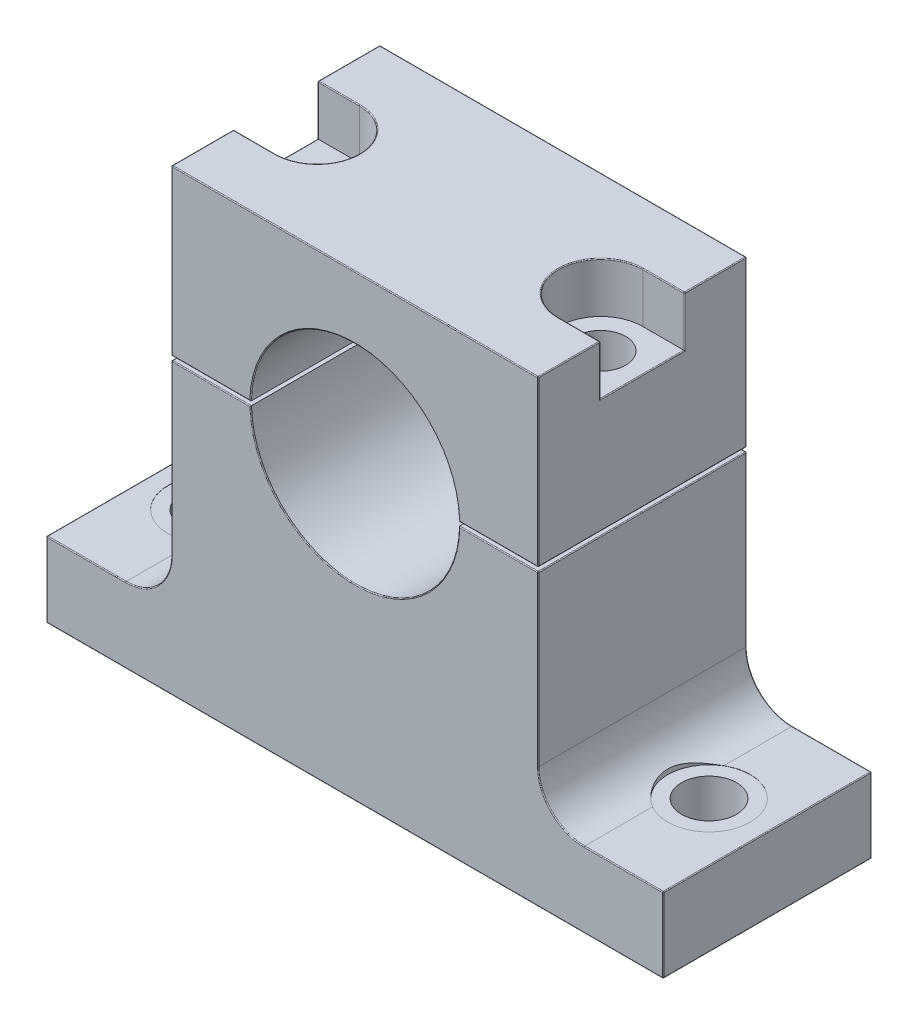
SolidWorks part; units mm, degrees
note: '?' marks a value the reader was unsure of.
material "ABS"
ref_plane "Front Plane" through (0, 0, 0) normal (0, 0, 1) x (1, 0, 0)
ref_plane "Top Plane" through (0, 0, 0) normal (0, 1, 0) x (1, 0, 0)
ref_plane "Right Plane" through (0, 0, 0) normal (1, 0, 0) x (0, 0, -1)
sketch "Sketch1" plane through (0, 0, 0) normal (0, 0, 1) x (1, 0, 0)
  line L0 (0, 20) -> (0, -35) construction
  line L1 (37, -35) -> (-37, -35) construction
  line L2 (-22, 20) -> (22, 20) construction
  line L3 (0, 0.25) -> (0, -0.25) construction
  line L4 (-17, 0) -> (17, 0) construction
  line L5 (-30, -26) -> (30, -26) construction
  line L6 (-17, 20) -> (-17, -35) construction
  line L7 (-22, 20) -> (-12, 20) construction
  line L8 (-20, -35) -> (-14, -35) construction
  line L9 (-33.3, -26) -> (-26.7, -26) construction
  line L10 (-34.95, -26) -> (-25.05, -26) construction
  circle A0 centre (0, 0) radius 12.5 construction
  point P7 (0, 0)
  point P8 (0, -35)
  point P11 (0, -26)
  point P14 (0, 20)
  point P15 (0, 0)
  point P20 (0, -26)
  point P23 (-17, 14)
  point P26 (-17, 20)
  point P27 (-17, -35)
  point P30 (-30, -26)
  point P35 (-30, -26)
  dimension "D1" = 0.5
  dimension "D3" = 6
  dimension "D4" = 9.9
sketch "Sketch2" plane through (0, 0, 0) normal (0, 0, 1) x (1, 0, 0)
  line L0 (-22, 20) -> (22, 20)
  line L1 (37, -35) -> (-37, -35) construction
  line L2 (37, -35) -> (-37, -35)
  line L3 (-37, -35) -> (-37, -26)
  line L4 (-37, -26) -> (-27.5, -26)
  line L5 (-22, -20.5) -> (-22, -0.25)
  line L6 (22, 20) -> (22, 0.25)
  line L7 (27.5, -26) -> (37, -26)
  line L8 (37, -26) -> (37, -35)
  line L9 (-22, 0.25) -> (-12.4975, 0.25)
  line L10 (-22, -0.25) -> (-12.4975, -0.25)
  line L11 (-22, 0.25) -> (-22, 20)
  line L12 (22, -0.25) -> (22, -20.5)
  line L13 (12.4975, 0.25) -> (22, 0.25)
  line L14 (12.4975, -0.25) -> (22, -0.25)
  circle A0 centre (0, 0) radius 12.5 construction
  arc A1 (-12.4975, -0.25) -> (12.4975, -0.25) centre (0, 0) ccw
  arc A2 (12.4975, 0.25) -> (-12.4975, 0.25) centre (0, 0) ccw
  arc A3 (22, -20.5) -> (27.5, -26) centre (27.5, -20.5) ccw
  arc A4 (-27.5, -26) -> (-22, -20.5) centre (-27.5, -20.5) ccw
  dimension "D1" = 5.5
extrude "Boss-Extrude1" add sketch "Sketch2" along normal mid plane 25
sketch "Sketch3" plane through (0, -26, 0) normal (0, 1, 0) x (1, 0, 0)
  line L0 (37, 0) -> (-37, 0) construction
  line L1 (-17, 0) -> (17, 0) construction
  circle A0 centre (-17, 0) radius 5
  circle A1 centre (17, 0) radius 5
  circle A2 centre (-30, 0) radius 3.3
  circle A3 centre (30, 0) radius 3.3
  circle A4 centre (-30, 0) radius 4.95 construction
  circle A5 centre (30, 0) radius 4.95 construction
  circle A6 centre (-17, 0) radius 5 construction
  circle A9 centre (17, 0) radius 5 construction
  point P6 (0, 0)
  point P16 (0, 0)
sketch "Sketch4" plane through (0, -26, 0) normal (0, 1, 0) x (1, 0, 0)
  circle A0 centre (-30, 0) radius 3.3 construction
  circle A1 centre (30, 0) radius 3.3 construction
  circle A2 centre (-30, 0) radius 3.3
  circle A3 centre (30, 0) radius 3.3
  point P0 (-30, 0)
extrude "Cut-Extrude1" cut sketch "Sketch4" against normal through all
sketch "Sketch5" plane through (0, -26, 0) normal (0, 1, 0) x (1, 0, 0)
  circle A0 centre (30, 0) radius 4.95 construction
  circle A1 centre (-30, 0) radius 4.95 construction
  circle A2 centre (30, 0) radius 4.95
  circle A3 centre (-30, 0) radius 4.95
extrude "Cut-Extrude2" cut sketch "Sketch5" against normal blind 0.02 and the other way through all
sketch "Sketch6" plane through (0, 20, 0) normal (0, 1, 0) x (1, 0, 0)
  circle A0 centre (17, 0) radius 5 construction
  circle A1 centre (-17, 0) radius 5 construction
  circle A2 centre (17, 0) radius 5 construction
  circle A3 centre (-17, 0) radius 5 construction
  circle A4 centre (-17, 0) radius 5.05
  circle A5 centre (17, 0) radius 5.05
  dimension "D1" = 0.05
extrude "Cut-Extrude3" cut sketch "Sketch6" against normal up to vertex (6 mm away) up to point (-17, 14, 0)
sketch "Sketch12" plane through (0, 20, 0) normal (0, 1, 0) x (1, 0, 0)
  line L0 (-17, 5.05) -> (-22, 5.05)
  line L1 (-22, -12.5) -> (-22, -0.7089) construction
  line L2 (-22, 5.05) -> (-22, -5.05)
  line L3 (-22, -12.5) -> (-22, 12.5) construction
  line L4 (-22, -5.05) -> (-17, -5.05)
  line L5 (0, 12.5) -> (0, -12.5) construction
  line L6 (22, 12.5) -> (-22, 12.5) construction
  line L7 (22, -12.5) -> (-22, -12.5) construction
  line L8 (22, -5.05) -> (17, -5.05)
  line L9 (22, 5.05) -> (22, -5.05)
  line L10 (17, 5.05) -> (22, 5.05)
  arc A1 (-17, -5.05) -> (-17, 5.05) centre (-17, 0) ccw
  arc A2 (17, -5.05) -> (17, 5.05) centre (17, 0) cw
  circle A4 centre (-17, 0) radius 5.05 construction
extrude "Cut-Extrude6" cut sketch "Sketch12" against normal up to vertex (6 mm away) up to point (-17, 14, 0)
sketch "Sketch8" plane through (0, 20, 0) normal (0, 1, 0) x (1, 0, 0)
  circle A2 centre (17, 0) radius 3
  circle A3 centre (-17, 0) radius 3
extrude "Cut-Extrude4" cut sketch "Sketch8" against normal through all
sketch "Sketch10" plane through (0, 0, 0) normal (0, 0, 1) x (1, 0, 0)
  line L4 (-17, 20) -> (-12, 20)
  line L5 (-12, 20) -> (-12, 14)
  line L6 (-12, 14) -> (-14, 14)
  line L7 (-14, 14) -> (-14, -35)
  line L10 (-14, -35) -> (-17, -35)
  line L11 (-17, -35) -> (-17, 20)
revolve "Revolve1" [suppressed] add sketch "Sketch10" angle 360 about L11
sketch "Sketch11" [suppressed] plane through (0, 20, 0) normal (0, 1, 0) x (1, 0, 0)
  line L0 (-17, 0) -> (-17, 2.5) construction
  line L1 (-17, 2.5) -> (-19.1651, 1.25)
  line L2 (-19.1651, 1.25) -> (-19.1651, -1.25)
  line L3 (-19.1651, -1.25) -> (-17, -2.5)
  line L4 (-17, -2.5) -> (-14.8349, -1.25)
  line L5 (-14.8349, -1.25) -> (-14.8349, 1.25)
  line L6 (-14.8349, 1.25) -> (-17, 2.5)
  line L7 (-17, 5) -> (-17, 2.5) construction
  circle A0 centre (-17, 0) radius 2.1651 construction
  circle A2 centre (-17, 0) radius 5 construction
  circle A3 centre (-17, 0) radius 5 construction
  dimension "D1" = 10
extrude "Cut-Extrude5" [suppressed] cut sketch "Sketch11" against normal blind 3
chamfer "Chamfer1" [suppressed] distance 0.6 angle 45
mirror "Mirror1" [suppressed] about plane through (0, 0, 0) normal (1, 0, 0)
fillet "Fillet1" radius 0.1 30 edges at (32.25, -26, -12.5) (23.6109, -24.3891, -12.5) (17.2487, -0.25, -12.5) (0, -12.5, -12.5) (-17.2487, -0.25, -12.5) (-23.6109, -24.3891, -12.5) (-32.25, -26, -12.5) (0, -35, -12.5) (22, -0.25, 0) (22, -10.375, -12.5) (37, -26, 0) (37, -30.5, -12.5) (37, -35, 0) (-37, -26, 0) (-37, -35, 0) (-37, -30.5, -12.5) (-22, -0.25, 0) (-22, -10.375, -12.5) (0, -35, 12.5) (-37, -30.5, 12.5) (-32.25, -26, 12.5) (-23.6109, -24.3891, 12.5) (-22, -10.375, 12.5) (-17.2487, -0.25, 12.5) (0, -12.5, 12.5) (17.2487, -0.25, 12.5) (22, -10.375, 12.5) (23.6109, -24.3891, 12.5) (32.25, -26, 12.5) (37, -30.5, 12.5)
fillet "Fillet2" radius 0.1 30 edges at (22, 0.25, 0) (-22, 0.25, 0) (-17.2487, 0.25, -12.5) (0, 12.5, -12.5) (17.2487, 0.25, -12.5) (22, 10.125, -12.5) (-22, 10.125, -12.5) (-22, 20, 8.775) (-22, 20, -8.775) (0, 20, -12.5) (22, 20, -8.775) (22, 20, 8.775) (0, 20, 12.5) (22, 10.125, 12.5) (17.2487, 0.25, 12.5) (0, 12.5, 12.5) (-17.2487, 0.25, 12.5) (-22, 10.125, 12.5) (-19.5, 20, -5.05) (19.5, 20, -5.05) (19.5, 20, 5.05) (-19.5, 20, 5.05) (22, 17, 5.05) (22, 17, -5.05) (-22, 17, 5.05) (-22, 17, -5.05) (22, 14, 0) (-22, 14, 0) (-11.95, 20, 0) (11.95, 20, 0)
ref_plane "Contact Plane 1" through (0, -35, 0) normal (0, -1, 0) x (-1, 0, 0)
ref_axis "Center Axis 1" through (0, 0, 12.4) along (0, 0, -1)?
split "Split1" trim tools "Top Plane" bodies to split 109 128 resulting bodies 130 131
equation "\"D3@Sketch1\"=\"G@Sketch1\""
equation "\"D4@Sketch1\"=\"K@Sketch1\"*1.5"
equation "\"D1@Sketch2\"=\"Height@Sketch1\"*.1"
